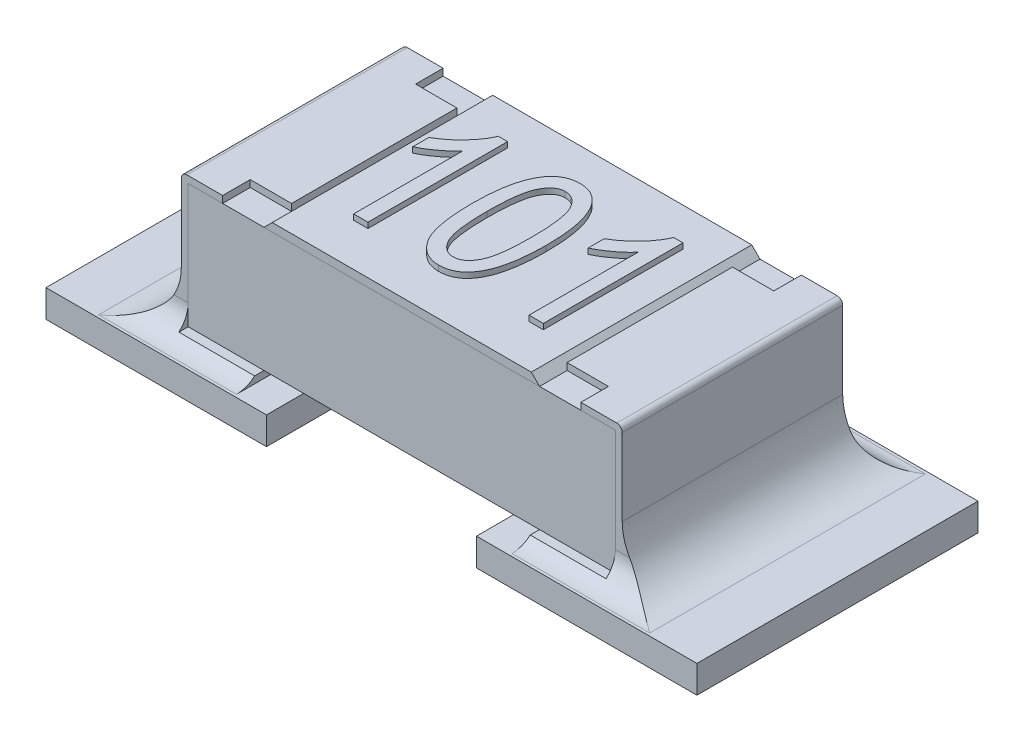
SolidWorks part; units mm, degrees
material "Ceramic Porcelain"
ref_plane "Front Plane" through (0, 0, 0) normal (0, 0, 1) x (1, 0, 0)
ref_plane "Top Plane" through (0, 0, 0) normal (0, 1, 0) x (1, 0, 0)
ref_plane "Right Plane" through (0, 0, 0) normal (1, 0, 0) x (0, 0, -1)
sketch "Sketch1" plane through (0, 0, 0) normal (1, 0, 0) x (0, 0, -1)
  line L0 (0, 55) -> (0, -55) construction
  line L1 (-0.4, 0.575) -> (0.4, 0.575)
  line L2 (-0.4, 0.575) -> (-0.4, 0.125)
  line L3 (-0.4, 0.125) -> (0.4, 0.125)
  line L4 (0.4, 0.575) -> (0.4, 0.125)
  line L5 (55, 0) -> (-55, 0) construction
  dimension "D1" = 0.8
  dimension "D2" = 0.4
  dimension "D3" = 0.45
  dimension "D4" = 0.125
extrude "Boss-Extrude1" add sketch "Sketch1" along normal mid plane 1.55
sketch "Sketch2" plane through (0, 0, 0) normal (0, 0, 1) x (1, 0, 0)
  line L0 (-0.5, 0.6) -> (-0.78, 0.6)
  line L1 (-0.8, 0.58) -> (-0.8, 0.1)
  line L2 (-0.8, 0.1) -> (-0.5, 0.1)
  line L3 (-0.5, 0.1) -> (-0.5, 0.125)
  line L4 (0.775, 0.125) -> (-0.775, 0.125) construction
  line L5 (-0.5, 0.125) -> (-0.775, 0.125)
  line L6 (-0.775, 0.125) -> (-0.775, 0.575)
  line L7 (-0.775, 0.575) -> (-0.5, 0.575)
  line L8 (0.775, 0.575) -> (-0.775, 0.575) construction
  line L9 (-0.5, 0.575) -> (-0.5, 0.6)
  line L11 (0.5, 0.575) -> (0.5, 0.6)
  line L12 (0.5, 0.6) -> (0.78, 0.6)
  line L13 (0.8, 0.58) -> (0.8, 0.1)
  line L14 (0.8, 0.1) -> (0.5, 0.1)
  line L15 (0.5, 0.1) -> (0.5, 0.125)
  line L16 (0.5, 0.125) -> (0.775, 0.125)
  line L17 (0.775, 0.125) -> (0.775, 0.575)
  line L18 (0.775, 0.575) -> (0.5, 0.575)
  arc A0 (0.78, 0.6) -> (0.8, 0.58) centre (0.78, 0.58) cw
  arc A1 (-0.78, 0.6) -> (-0.8, 0.58) centre (-0.78, 0.58) ccw
  point P28 (-0.8, 0.6)
  dimension "D6" = 0.02
  dimension "D1" = 0.025
  dimension "D2" = 0.025
  dimension "D3" = 0.025
  dimension "D4" = 0.3
  dimension "D5" = 0.3
extrude "Boss-Extrude2" add sketch "Sketch2" along normal mid plane 0.8 separate body
sketch "Sketch3" plane through (0, 0.6, 0) normal (0, 1, 0) x (1, 0, 0)
  line L0 (0.5, -0.4) -> (0.5, 0.4) construction
  line L1 (-0.5, 0.4) -> (-0.65, 0.4)
  line L2 (-0.5, 0.4) -> (-0.5, 0.3)
  line L3 (-0.5, 0.3) -> (-0.65, 0.3)
  line L4 (-0.65, 0.4) -> (-0.65, 0.3)
  line L5 (-0.5, -0.4) -> (-0.65, -0.4)
  line L6 (-0.5, -0.4) -> (-0.5, -0.3)
  line L7 (-0.5, -0.3) -> (-0.65, -0.3)
  line L8 (-0.65, -0.4) -> (-0.65, -0.3)
  line L9 (0.5, -0.4) -> (0.65, -0.4)
  line L10 (0.5, -0.4) -> (0.5, -0.3)
  line L11 (0.5, -0.3) -> (0.65, -0.3)
  line L12 (0.65, -0.4) -> (0.65, -0.3)
  line L13 (0.775, -0.4) -> (-0.775, -0.4) construction
  line L15 (0.5, 0.4) -> (0.65, 0.4)
  line L16 (0.5, 0.4) -> (0.5, 0.3)
  line L17 (0.5, 0.3) -> (0.65, 0.3)
  line L18 (0.65, 0.4) -> (0.65, 0.3)
  dimension "D1" = 0.15
  dimension "D2" = 0.1
extrude "Cut-Extrude1" cut sketch "Sketch3" against normal blind 0.025
sketch "Sketch4" plane through (0, 0, 0) normal (0, 0, 1) x (1, 0, 0)
  line L0 (-0.5, 0.575) -> (0.5, 0.575)
  line L1 (0.5, 0.575) -> (0.47, 0.605)
  line L2 (0.47, 0.605) -> (-0.47, 0.605)
  line L3 (-0.47, 0.605) -> (-0.5, 0.575)
  dimension "D1" = 45
  dimension "D2" = 45
  dimension "D3" = 0.03
extrude "Boss-Extrude3" add sketch "Sketch4" along normal mid plane 0.8 separate body
sketch "Sketch7" plane through (0, 0, 0) normal (0, 1, 0) x (1, 0, 0)
  line L0 (0, -0.2833) -> (0, 0.2833) construction
  line L1 (-0.381, -0.51) -> (-1.181, -0.51)
  line L2 (-0.381, -0.51) -> (-0.381, 0.51)
  line L3 (-0.381, 0.51) -> (-1.181, 0.51)
  line L4 (-1.181, -0.51) -> (-1.181, 0.51)
  line L5 (0.381, -0.51) -> (1.181, -0.51)
  line L6 (0.381, -0.51) -> (0.381, 0.51)
  line L7 (0.381, 0.51) -> (1.181, 0.51)
  line L8 (1.181, -0.51) -> (1.181, 0.51)
  line L9 (-0.2833, 0) -> (0.2833, 0) construction
  dimension "D1" = 0.8
  dimension "D2" = 0.381
  dimension "D3" = 0.381
  dimension "D4" = 1.02
  dimension "D5" = 0.51
extrude "Boss-Extrude5" add sketch "Sketch7" along normal blind 0.1
fillet "Fillet3" radius 0.2 1 edges at (-0.8, 0.1, 0)
fillet "Fillet4" radius 0.2 1 edges at (0.8, 0.1, 0)
fillet "Fillet5" radius 0.1 2 edges at (0.75, 0.1, -0.4) (0.75, 0.1, 0.4)
fillet "Fillet6" radius 0.1 2 edges at (-0.75, 0.1, 0.4) (-0.75, 0.1, -0.4)
sketch "Esquisse2" plane through (0, 0.605, 0) normal (0, 1, 0) x (1, 0, 0)
  text T0 "101" font "Arial Narrow" height 0.5
extrude "Boss.-Extru.1" add sketch "Esquisse2" along normal blind 0.02
